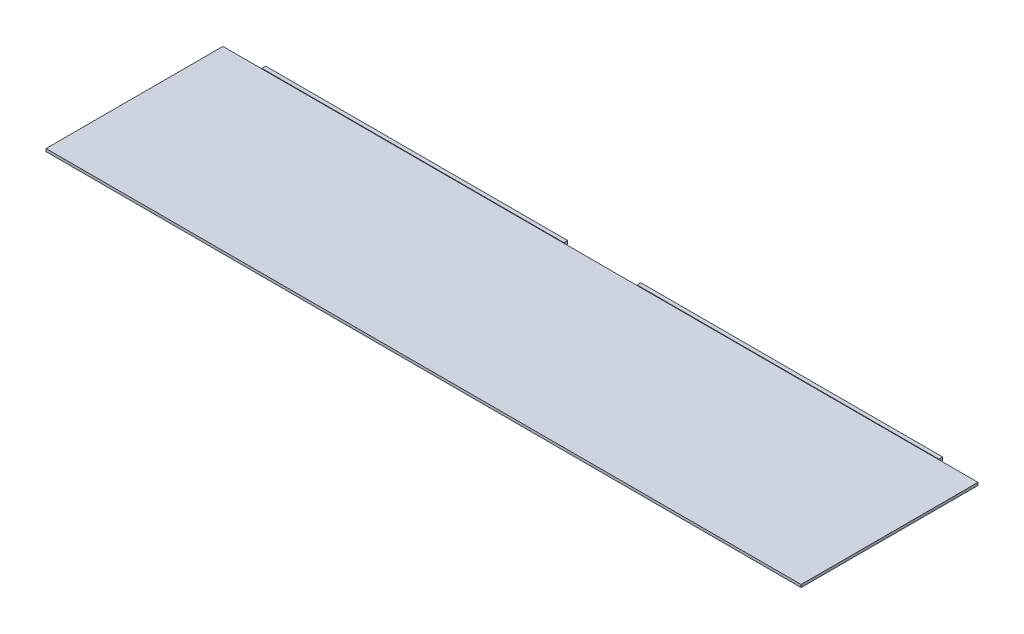
SolidWorks part; units mm, degrees
material "6061-T6 (SS)"
ref_plane "X-Y Datum" through (0, 0, 0) normal (0, 0, 1) x (1, 0, 0)
ref_plane "X-Z Datum" through (0, 0, 0) normal (0, 1, 0) x (1, 0, 0)
ref_plane "Y-Z Datum" through (0, 0, 0) normal (1, 0, 0) x (0, 0, -1)
sketch "Sketch1" plane through (0, 0, 0) normal (0, 1, 0) x (1, 0, 0)
  line L1 (-317.6778, 74.422) -> (317.6778, 74.422)
  line L2 (-317.6778, 74.422) -> (-317.6778, -74.422)
  line L3 (-317.6778, -74.422) -> (317.6778, -74.422)
  line L4 (317.6778, 74.422) -> (317.6778, -74.422)
  line L5 (-317.6778, 74.422) -> (317.6778, -74.422) construction
  line L6 (-317.6778, -74.422) -> (317.6778, 74.422) construction
  point P0 (0, 0)
  dimension "D1" = 635.3556
  dimension "D2" = 148.844
extrude "Boss-Extrude1" add sketch "Sketch1" along normal mid plane 2.286
sketch "Sketch2" plane through (0, 0, -74.422) normal (0, 0, -1) x (-1, 0, 0)
  line L20 (-317.6778, -1.143) -> (317.6778, -1.143) construction
  line L21 (-284.8229, -1.143) -> (-30.8229, -1.143)
  line L22 (30.8229, -1.143) -> (284.8229, -1.143)
  line L40 (30.8229, -1.143) -> (30.8229, 1.5875)
  line L41 (30.8229, 1.5875) -> (284.8229, 1.5875)
  line L42 (284.8229, 1.5875) -> (284.8229, -1.143)
  line L56 (-284.8229, -1.143) -> (-284.8229, 1.5875)
  line L57 (-284.8229, 1.5875) -> (-30.8229, 1.5875)
  line L58 (-30.8229, 1.5875) -> (-30.8229, -1.143)
extrude "Boss-Extrude2" add sketch "Sketch2" along normal blind 3.175
